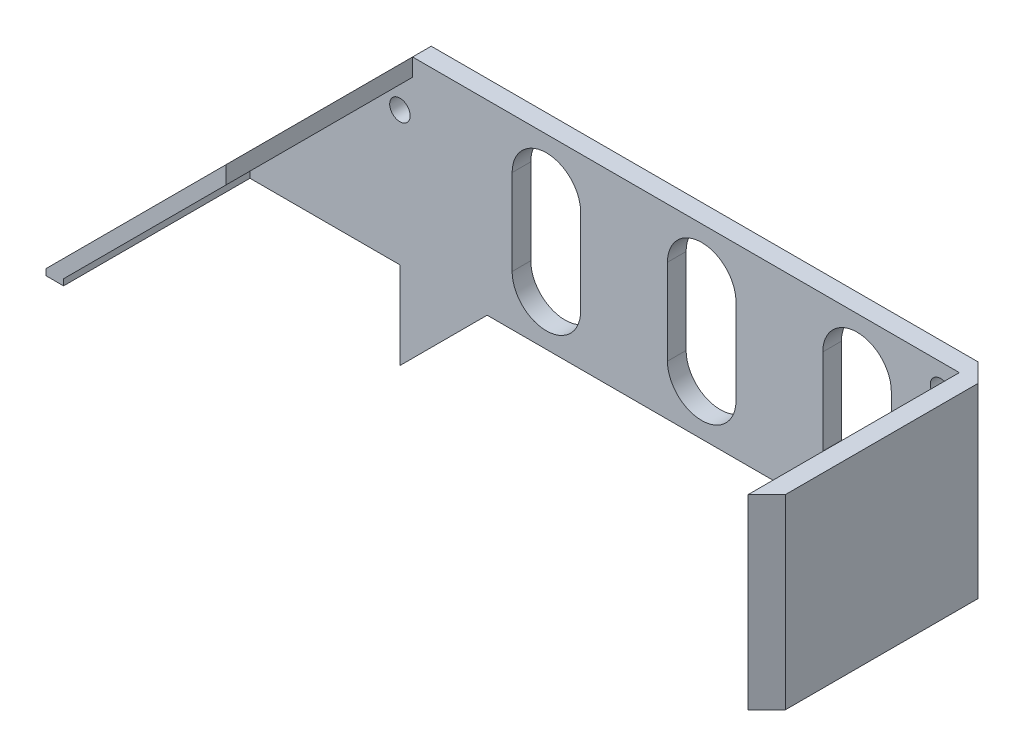
SolidWorks part; units mm, degrees
ref_plane "前视基准面" through (0, 0, 0) normal (0, 0, 1) x (1, 0, 0)
ref_plane "上视基准面" through (0, 0, 0) normal (0, 1, 0) x (1, 0, 0)
ref_plane "右视基准面" through (0, 0, 0) normal (1, 0, 0) x (0, 0, -1)
other "Configuration Table"
sketch "草图1" plane through (0, 0, 0) normal (0, 0, 1) x (1, 0, 0)
  line L1 (0, 0) -> (100, 0)
  line L2 (0, 0) -> (0, 30)
  line L3 (0, 30) -> (100, 30)
  line L4 (100, 0) -> (100, 30)
  dimension "D1" = 100
  dimension "D2" = 30
extrude "凸台-拉伸1" add sketch "草图1" along normal blind 3
sketch "草图2" plane through (0, 0, 3) normal (0, 0, 1) x (1, 0, 0)
  line L0 (0, 18) -> (12, 30)
  line L1 (0, 30) -> (0, 0) construction
  line L2 (100, 30) -> (0, 30) construction
  line L3 (12, 30) -> (0, 30)
  line L4 (0, 30) -> (0, 18)
  line L5 (-18, 0) -> (12, 30) construction
extrude "切除-拉伸1" cut sketch "草图2" against normal up to next
sketch "草图3" plane through (0, 0, 0) normal (0, 0, -1) x (-1, 0, 0)
  line L0 (-24, 0) -> (-10, -14) construction
  line L1 (-24, 0) -> (-10, -14)
  line L2 (-10, -14) -> (-10, 0)
  line L3 (0, 0) -> (-100, 0) construction
  line L4 (-10, 0) -> (-24, 0)
sketch "草图4" plane through (0, 0, 0) normal (0, 0, -1) x (-1, 0, 0)
  line L0 (0, 0) -> (17, 0)
  line L1 (17, 1) -> (0, 18)
  line L2 (0, 18) -> (0, 0)
  line L3 (17, 0) -> (17, 1)
extrude "凸台-拉伸3" add sketch "草图4" against normal blind 3
sketch "草图5" plane through (0, 0, 3) normal (0, 0, 1) x (1, 0, 0)
  circle A0 centre (9.9634, 21.5937) radius 1.65
  circle A1 centre (97, 26) radius 1.6838
  circle A2 centre (97, 4) radius 1.65
extrude "切除-拉伸2" cut sketch "草图5" against normal up to next
sketch "草图6" plane through (0, 0, 3) normal (0, 0, 1) x (1, 0, 0)
  line L1 (100, 0) -> (103, 0)
  line L2 (100, 0) -> (100, 30)
  line L3 (100, 30) -> (103, 30)
  line L4 (103, 0) -> (103, 30)
  dimension "D1" = 3
extrude "凸台-拉伸4" add sketch "草图6" along normal blind 34 and the other way blind 3
sketch "草图7" plane through (0, 0, 3) normal (0, 0, 1) x (1, 0, 0)
  line L0 (-17, 1) -> (12, 30) construction
  line L1 (-17, 1) -> (12, 30)
  line L3 (-14.1716, 1) -> (12, 27.1716)
  line L4 (12, 27.1716) -> (12, 30)
  line L5 (-14.1716, 1) -> (-14.1716, 0)
  line L6 (-17, 0) -> (100, 0) construction
  line L7 (-14.1716, 0) -> (-17, 0)
  line L8 (-17, 0) -> (-17, 1)
  dimension "D1" = 2
extrude "凸台-拉伸5" add sketch "草图7" along normal blind 30
chamfer "倒角1" distance 3 angle 45 1 edges at (103, 15, 0)
chamfer "倒角2" distance 3 angle 45 1 edges at (103, 15, 37)
extrude "凸台-拉伸6" add sketch "草图3" against normal blind 3
sketch "草图8" plane through (0, 0, 0) normal (0, 0, -1) x (-1, 0, 0)
  line L0 (-83.5344, 21.8947) -> (-83.5344, 8.1053) construction
  line L1 (-78.0217, 21.8947) -> (-78.0217, 8.1053)
  line L2 (-89.0471, 21.8947) -> (-89.0471, 8.1053)
  line L3 (-58.5344, 21.8947) -> (-58.5344, 8.1053) construction
  line L4 (-53.0217, 21.8947) -> (-53.0217, 8.1053)
  line L5 (-64.0471, 21.8947) -> (-64.0471, 8.1053)
  line L6 (-33.5344, 21.8947) -> (-33.5344, 8.1053) construction
  line L7 (-28.0217, 21.8947) -> (-28.0217, 8.1053)
  line L8 (-39.0471, 21.8947) -> (-39.0471, 8.1053)
  arc A0 (-78.0217, 21.8947) -> (-89.0471, 21.8947) centre (-83.5344, 21.8947) ccw
  arc A1 (-89.0471, 8.1053) -> (-78.0217, 8.1053) centre (-83.5344, 8.1053) ccw
  arc A2 (-53.0217, 21.8947) -> (-64.0471, 21.8947) centre (-58.5344, 21.8947) ccw
  arc A3 (-64.0471, 8.1053) -> (-53.0217, 8.1053) centre (-58.5344, 8.1053) ccw
  arc A4 (-28.0217, 21.8947) -> (-39.0471, 21.8947) centre (-33.5344, 21.8947) ccw
  arc A5 (-39.0471, 8.1053) -> (-28.0217, 8.1053) centre (-33.5344, 8.1053) ccw
  point P2 (-83.5344, 15)
  point P11 (-58.5344, 15)
  point P18 (-33.5344, 15)
  dimension "D1" = 3
extrude "切除-拉伸3" cut sketch "草图8" against normal through all
